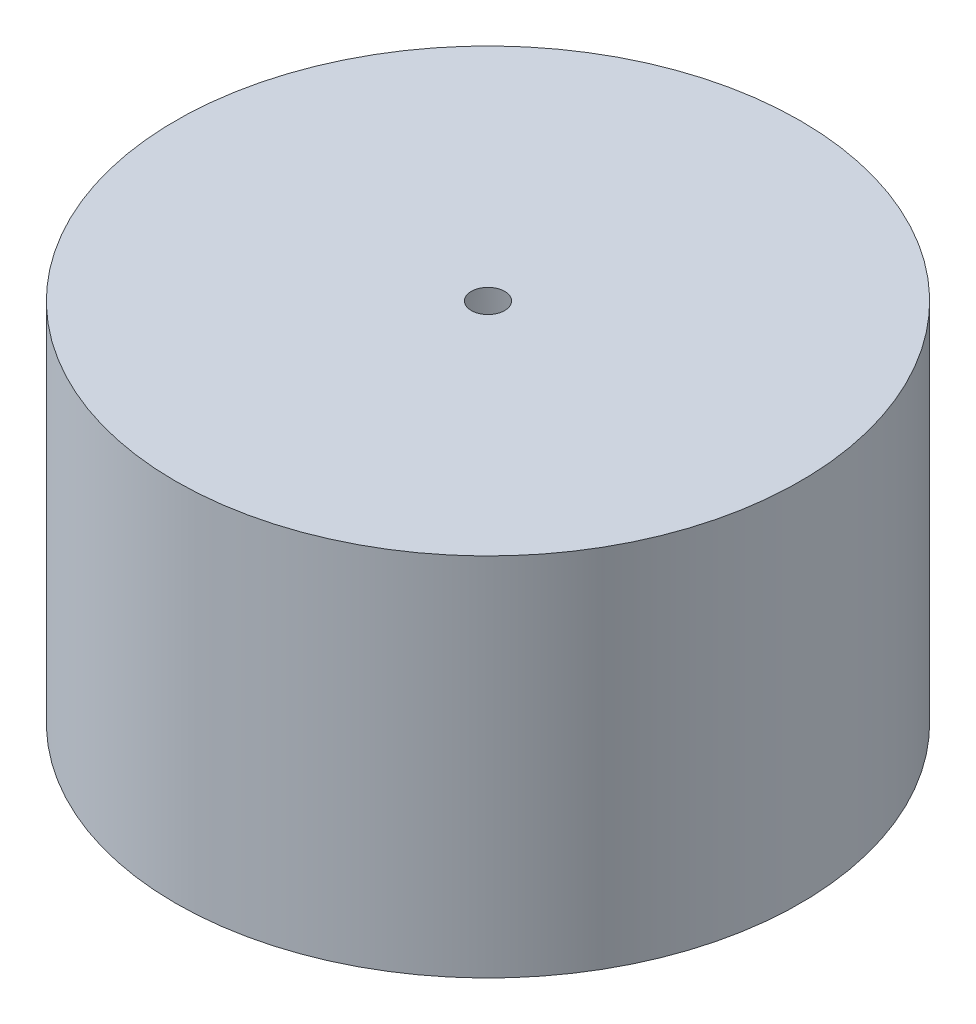
SolidWorks part; units mm, degrees
ref_plane "Спереди" through (0, 0, 0) normal (0, 0, 1) x (1, 0, 0)
ref_plane "Сверху" through (0, 0, 0) normal (0, 1, 0) x (1, 0, 0)
ref_plane "Справа" through (0, 0, 0) normal (1, 0, 0) x (0, 0, -1)
sketch "Эскиз1" plane through (0, 0, 0) normal (0, 0, 1) x (1, 0, 0)
  line L0 (0, 0) -> (0, 64.3029) construction
  line L33 (30, 28.7946) -> (30, 26.2946)
  line L34 (30, 26.2946) -> (28.4, 26.2946)
  line L35 (28.4, 26.2946) -> (28.4, 18.2946)
  line L37 (8, 58.6338) -> (2, 62.0979)
  line L38 (2, 62.0979) -> (37.4277, 62.0979)
  line L40 (28.4, 18.2946) -> (37.4277, 18.2946)
  line L41 (37.4277, 18.2946) -> (37.4277, 62.0979)
  line L42 (8, 58.6338) -> (8.3476, 52.0019)
  line L43 (8.3476, 52.0019) -> (10.7476, 49.4019)
  line L44 (8, 58.6338) -> (8, 51.4355) construction
  line L45 (10.7476, 49.4019) -> (10.9571, 43.4008)
  line L46 (10.7476, 49.4019) -> (10.7476, 37.0019) construction
  line L47 (11.9976, 33.9946) -> (11.9976, 40.6046) construction
  line L49 (11.9976, 40.6046) -> (12.2284, 33.9946)
  line L50 (12.2284, 33.9946) -> (19.2771, 33.9946) construction
  line L51 (12.2284, 33.9946) -> (16.2284, 29.9946)
  line L53 (30, 28.7946) -> (30, 29.9946)
  line L54 (16.2284, 29.9946) -> (30, 29.9946)
  arc A0 (11.9976, 40.6046) -> (10.9571, 43.4008) centre (11.33, 41.9479) ccw
  point P8 (10.9083, 44.8)
  point P11 (11.33, 41.9479)
  point P15 (0, 62.0979)
  point P17 (11.9976, 38.5019)
  dimension "D5" = 16
  dimension "D14" = 3
  dimension "D7" = 6.61
  dimension "D3" = 2.6
  dimension "D4" = 3
  dimension "D6" = 60
  dimension "D8" = 4
  dimension "D9" = 2
  dimension "D10" = 2.4
  dimension "D11" = 2
  dimension "D12" = 20.15
  dimension "D13" = 11.33
  dimension "D15" = 1.25
  dimension "D16" = 10.9
  dimension "D17" = 4
  dimension "D20" = 2.5
  dimension "D21" = 8
  dimension "D23" = 1.6
  dimension "D24" = 43
  dimension "D25" = 8.7973
  dimension "D26" = 6.0011
revolve "Повернуть1" add sketch "Эскиз1" angle 360 about L0 reverse direction yes
